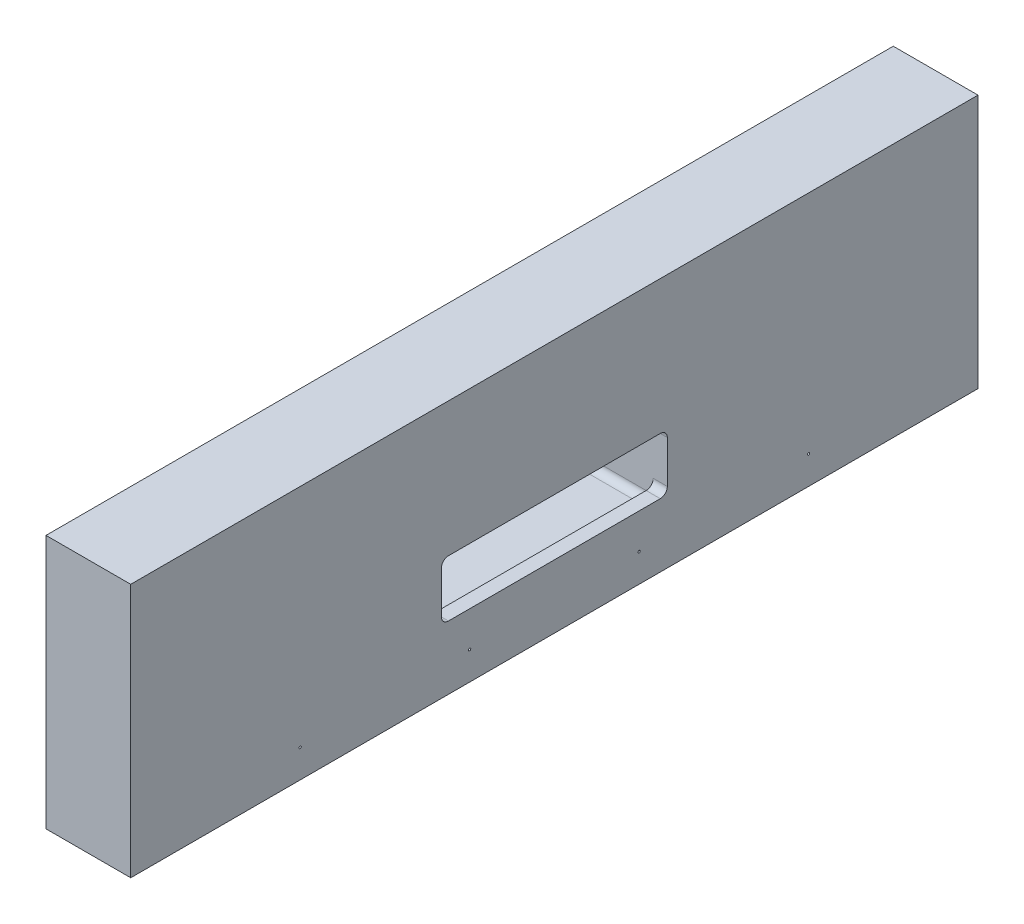
SolidWorks part; units mm, degrees
material "Maple"
ref_plane "Front Plane" through (0, 0, 0) normal (0, 0, 1) x (1, 0, 0)
ref_plane "Top Plane" through (0, 0, 0) normal (0, 1, 0) x (1, 0, 0)
ref_plane "Right Plane" through (0, 0, 0) normal (1, 0, 0) x (0, 0, -1)
sketch "Sketch1" plane through (0, 0, 0) normal (1, 0, 0) x (0, 0, -1)
  line L1 (0, 0) -> (762, 0)
  line L2 (0, 0) -> (0, 228.6)
  line L3 (0, 228.6) -> (762, 228.6)
  line L4 (762, 0) -> (762, 228.6)
  dimension "D1" = 762
  dimension "D2" = 228.6
extrude "Boss-Extrude1" add sketch "Sketch1" along normal blind 76.2
sketch "Sketch2" plane through (0, 0, 0) normal (-1, 0, 0) x (0, 0, 1)
  line L1 (-482.6, 44.45) -> (-279.4, 44.45)
  line L2 (-482.6, 44.45) -> (-482.6, 139.7)
  line L3 (-482.6, 139.7) -> (-279.4, 139.7)
  line L4 (-279.4, 44.45) -> (-279.4, 139.7)
  line L6 (0, 0) -> (-762, 0) construction
  line L7 (-762, 0) -> (-762, 228.6) construction
  point P6 (-381, 139.7)
  dimension "D1" = 44.45
  dimension "D2" = 381
  dimension "D3" = 95.25
  dimension "D4" = 203.2
extrude "Cut-Extrude1" cut sketch "Sketch2" against normal blind 63.5
sketch "Sketch3" plane through (63.5, 0, 0) normal (-1, 0, 0) x (0, 0, 1)
  line L0 (-279.4, 44.45) -> (-279.4, 139.7) construction
  line L1 (-482.6, 107.95) -> (-279.4, 107.95)
  line L2 (-482.6, 107.95) -> (-482.6, 57.15)
  line L3 (-482.6, 57.15) -> (-279.4, 57.15)
  line L4 (-279.4, 107.95) -> (-279.4, 57.15)
  line L5 (-482.6, 44.45) -> (-279.4, 44.45) construction
  line L6 (-482.6, 139.7) -> (-482.6, 44.45) construction
  dimension "D1" = 12.7
  dimension "D2" = 50.8
extrude "Cut-Extrude2" cut sketch "Sketch3" against normal through all
fillet "Fillet1" radius 25.4 2 edges at (31.75, 139.7, -279.4) (31.75, 139.7, -482.6)
sketch "Sketch4" plane through (0, 0, 0) normal (-1, 0, 0) x (0, 0, 1)
  line L1 (-762, 0) -> (-762, 228.6) construction
  line L2 (0, 0) -> (-762, 0) construction
  circle A0 centre (-609.6, 25.4) radius 1.016
  dimension "D3" = 2.032
  dimension "D1" = 152.4
  dimension "D2" = 25.4
extrude "Cut-Extrude3" cut sketch "Sketch4" against normal through all
pattern_linear "LPattern1" count 4 spacing 152.4 along (0, 0, 1) of "Cut-Extrude3"
fillet "Fillet2" radius 6.35 4 edges at (69.85, 57.15, -482.6) (69.85, 107.95, -482.6) (69.85, 57.15, -279.4) (69.85, 107.95, -279.4)
fillet "Fillet3" radius 6.35 2 edges at (31.75, 44.45, -279.4) (31.75, 44.45, -482.6)
